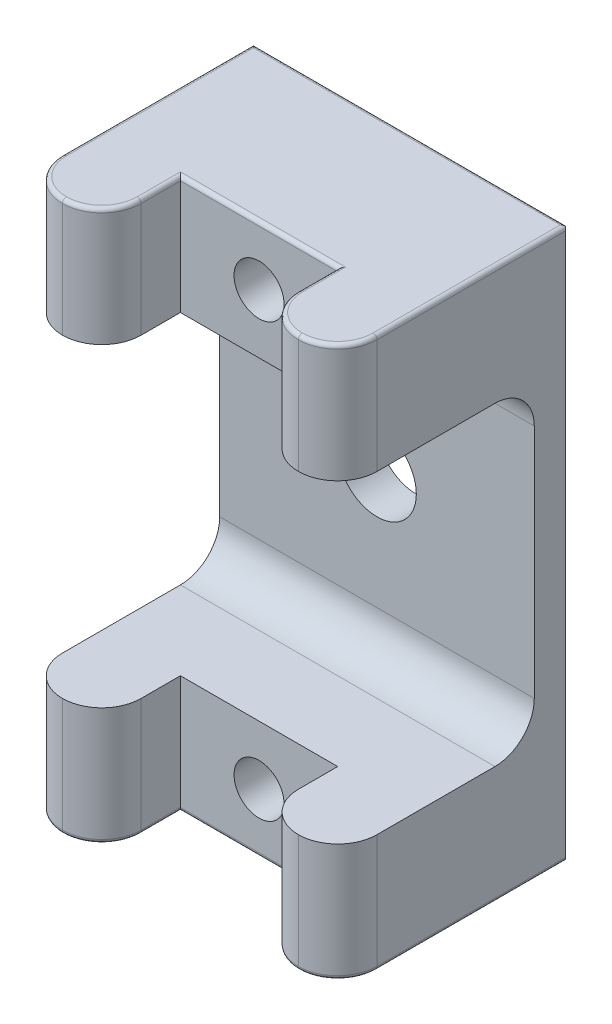
SolidWorks part; units mm, degrees
ref_plane "Front Plane" through (0, 0, 0) normal (0, 0, 1) x (1, 0, 0)
ref_plane "Top Plane" through (0, 0, 0) normal (0, 1, 0) x (1, 0, 0)
ref_plane "Right Plane" through (0, 0, 0) normal (1, 0, 0) x (0, 0, -1)
sketch "Sketch1" plane through (0, 0, 0) normal (0, 1, 0) x (1, 0, 0)
  line L1 (-12.7, 9.525) -> (12.7, 9.525)
  line L2 (-12.7, 9.525) -> (-12.7, -9.525)
  line L3 (-12.7, -9.525) -> (12.7, -9.525)
  line L4 (12.7, 9.525) -> (12.7, -9.525)
  line L5 (-12.7, 9.525) -> (12.7, -9.525) construction
  line L6 (-12.7, -9.525) -> (12.7, 9.525) construction
  point P0 (0, 0)
  dimension "D1" = 19.05
  dimension "D2" = 25.4
extrude "Boss-Extrude1" add sketch "Sketch1" along normal blind 44.45
sketch "Sketch2" plane through (12.7, 25.4, 0) normal (-1, 0, 0) x (0, 1, 0)
  line L1 (-15.875, -9.525) -> (9.525, -9.525)
  line L2 (-15.875, -9.525) -> (-15.875, 6.35)
  line L3 (-15.875, 6.35) -> (9.525, 6.35)
  line L4 (9.525, -9.525) -> (9.525, 6.35)
  line L5 (-3.175, -9.525) -> (-3.175, 9.525) construction
  line L7 (19.05, -9.525) -> (19.05, 9.525) construction
  line L8 (19.05, 9.525) -> (-25.4, 9.525) construction
  line L9 (19.05, -9.525) -> (-25.4, -9.525) construction
  dimension "D1" = 3.175
  dimension "D2" = 9.525
extrude "Cut-Extrude4" cut sketch "Sketch2" along normal through all
sketch "Sketch3" plane through (0, 44.45, 0) normal (0, 1, 0) x (1, 0, 0)
  line L0 (-12.7, -9.525) -> (12.7, -9.525) construction
  line L1 (-6.35, -9.525) -> (6.35, -9.525)
  line L2 (-6.35, -9.525) -> (-6.35, -3.175)
  line L3 (-6.35, -3.175) -> (6.35, -3.175)
  line L4 (6.35, -9.525) -> (6.35, -3.175)
  line L5 (-12.7, 9.525) -> (-12.7, -9.525) construction
  line L6 (0, -9.525) -> (0, 0) construction
  dimension "D1" = 6.35
  dimension "D2" = 6.35
extrude "Cut-Extrude5" cut sketch "Sketch3" against normal blind 50.8
fillet "Fillet1" radius 3.175 8 edges at (-12.7, 39.6875, 9.525) (-12.7, 4.7625, 9.525) (-6.35, 4.7625, 9.525) (12.7, 4.7625, 9.525) (6.35, 4.7625, 9.525) (12.7, 39.6875, 9.525) (6.35, 39.6875, 9.525) (-6.35, 39.6875, 9.525)
hole_wizard "#10-32 Tapped Hole1" positions "Sketch4" profile "Sketch5" tap size "#10-32" standard "ANSI Inch"
sketch "Sketch4" plane through (0, 0, 3.175) normal (0, 0, 1) x (1, 0, 0)
  line L0 (0, 4.7625) -> (0, 39.6875) construction
  line L2 (0, 39.6875) -> (0, 44.45) construction
  line L3 (6.35, 44.45) -> (-6.35, 44.45) construction
  line L6 (-12.7, 34.925) -> (-12.7, 9.525) construction
  line L7 (-12.7, 34.925) -> (-12.7, 9.525) construction
  line L8 (0, 22.225) -> (-12.7, 22.225) construction
  point P0 (0, 39.6875)
  point P2 (0, 4.7625)
  dimension "D1" = 34.925
sketch "Sketch5" plane through (0, 39.6875, 3.175) normal (1, 0, 0) x (0, -1, 0)
  line L0 (0, 0) -> (0, 6.5473)
  line L1 (0, 6.5473) -> (2.0193, 5.334)
  line L2 (2.0193, 5.334) -> (2.0193, 0)
  line L5 (2.0193, 0) -> (0, 0)
  line L10 (0, 6.5473) -> (-2.0193, 5.334) construction
  line L11 (0, -6.35) -> (0, 107.95) construction
  dimension "Tap Drill Dia." = 4.0386
  dimension "Tap Drill Depth" = 5.334
  dimension "Drill Angle" = 118
cosmetic thread "Hole Thread3" parameters "D1"=3.048, "D2"=4.826
cosmetic thread "Hole Thread4" parameters "D1"=3.048, "D2"=4.826
chamfer "Chamfer1" distance 0.635 angle 45 4 edges at (12.7, 22.225, -9.525) (0, 44.45, -9.525) (-12.7, 22.225, -9.525) (0, 0, -9.525)
hole_wizard "1/4 (0.25) Diameter Hole1" positions "Sketch6" profile "Sketch8" hole size "1/4" standard "ANSI Inch"
sketch "Sketch6" plane through (0, 0, -6.35) normal (0, 0, 1) x (1, 0, 0)
  line L1 (-12.7, 22.225) -> (12.7, 22.225)
  line L2 (-12.7, 34.925) -> (-12.7, 9.525) construction
  line L3 (12.7, 34.925) -> (12.7, 9.525) construction
  point P0 (0, 22.225)
sketch "Sketch8" plane through (0, 22.225, -6.35) normal (1, 0, 0) x (0, -1, 0)
  line L0 (0, 0) -> (0, 33.1497)
  line L1 (0, 33.1497) -> (3.175, 31.242)
  line L2 (3.175, 31.242) -> (3.175, 0)
  line L5 (3.175, 0) -> (0, 0)
  line L10 (0, 33.1497) -> (-3.175, 31.242) construction
  line L11 (0, -6.35) -> (0, 107.95) construction
  dimension "Hole Dia." = 6.35
  dimension "Hole Depth" = 31.242
  dimension "Drill Angle" = 118
fillet "Fillet2" radius 0.3175 20 edges at (-11.7701, 0, 8.5951) (-7.2799, 0, 8.5951) (-6.35, 0, 4.7625) (0, 0, 3.175) (6.35, 0, 4.7625) (7.2799, 0, 8.5951) (11.7701, 0, 8.5951) (12.7, 0, -1.27) (0, 0, -8.89) (-12.7, 0, -1.27) (11.7701, 44.45, 8.5951) (7.2799, 44.45, 8.5951) (6.35, 44.45, 4.7625) (0, 44.45, 3.175) (-6.35, 44.45, 4.7625) (-7.2799, 44.45, 8.5951) (-11.7701, 44.45, 8.5951) (-12.7, 44.45, -1.27) (0, 44.45, -8.89) (12.7, 44.45, -1.27)
fillet "Fillet3" radius 3.175 2 edges at (0, 9.525, -6.35) (0, 34.925, -6.35)
